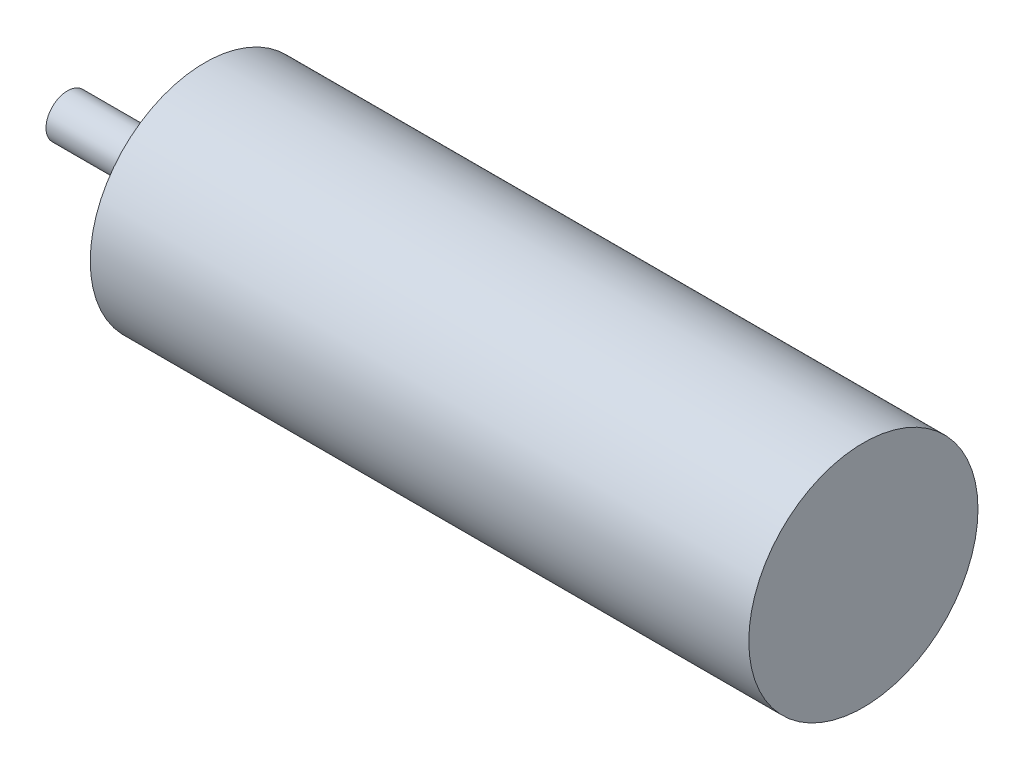
SolidWorks part; units mm, degrees
ref_plane "Front Plane" through (0, 0, 0) normal (0, 0, 1) x (1, 0, 0)
ref_plane "Top Plane" through (0, 0, 0) normal (0, 1, 0) x (1, 0, 0)
ref_plane "Right Plane" through (0, 0, 0) normal (1, 0, 0) x (0, 0, -1)
sketch "Sketch1" plane through (0, 0, 0) normal (0, 0, 1) x (1, 0, 0)
  line L0 (0, 0) -> (111.125, 0)
  line L1 (0, 0) -> (0, 3)
  line L2 (0, 3) -> (15.5, 3)
  line L3 (15.5, 3) -> (15.5, 9)
  line L4 (15.5, 9) -> (19.177, 9)
  line L5 (19.177, 9) -> (19.177, 16)
  line L6 (19.177, 16) -> (111.125, 16)
  line L7 (111.125, 16) -> (111.125, 0)
  dimension "D1" = 111.125
  dimension "D2" = 3
  dimension "D3" = 9
  dimension "D4" = 16
  dimension "D5" = 91.948
  dimension "D6" = 15.5
revolve "Revolve1" add sketch "Sketch1" angle 360 about L0
sketch "Sketch2" plane through (19.177, 0, 0) normal (-1, 0, 0) x (0, 0, 1)
  line L0 (0, 13) -> (0, -13) construction
  line L1 (-13, 0) -> (13, 0) construction
  circle A0 centre (0, 13) radius 1.5
  circle A1 centre (0, -13) radius 1.5
  circle A2 centre (-13, 0) radius 1.5
  circle A3 centre (13, 0) radius 1.5
  point P7 (0, 0)
  dimension "D1" = 26
  dimension "D2" = 3
extrude "Cut-Extrude1" cut sketch "Sketch2" against normal blind 5
